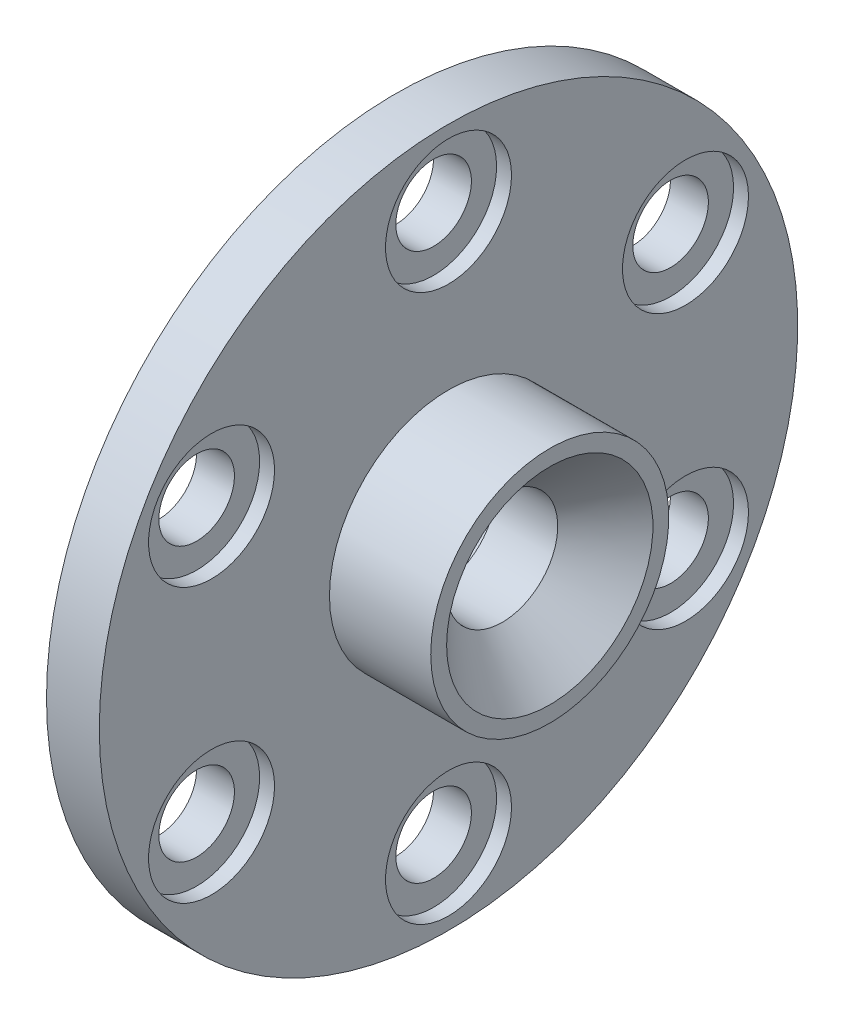
SolidWorks part; units mm, degrees
ref_plane "Front Plane" through (0, 0, 0) normal (0, 0, 1) x (1, 0, 0)
ref_plane "Top Plane" through (0, 0, 0) normal (0, 1, 0) x (1, 0, 0)
ref_plane "Right Plane" through (0, 0, 0) normal (1, 0, 0) x (0, 0, -1)
sketch "Sketch2" plane through (0, 0, 0) normal (0, 0, 1) x (1, 0, 0)
  line L0 (0, 0) -> (58.591, 0) construction
  line L2 (0, 0) -> (18.4, 0)
  line L3 (0, 0) -> (0, 2.5)
  line L4 (0, 2.5) -> (18.4, 2.5)
  line L5 (18.4, 0) -> (18.4, 2.5)
  line L6 (6.0094, 2.5) -> (6.0094, 6)
  line L11 (6.0094, 6) -> (9.9794, 6)
  line L16 (12.9794, 6) -> (12.9794, 3)
  line L17 (12.9794, 3) -> (13.6398, 3)
  line L18 (13.6398, 3) -> (13.6398, 2.5)
  line L19 (13.6398, 2.5) -> (6.0094, 2.5)
  line L22 (13.6398, 2.5) -> (16.1198, 2.5)
  line L23 (13.6398, 2.5) -> (13.6398, 4)
  line L24 (13.6398, 4) -> (16.1198, 4)
  line L25 (16.1198, 2.5) -> (16.1198, 4)
  line L27 (6.0094, 6) -> (9.9794, 6)
  line L28 (6.0094, 6) -> (6.0094, 9)
  line L29 (6.0094, 9) -> (9.9794, 9)
  line L30 (9.9794, 6) -> (9.9794, 9)
  line L31 (6.0094, 9) -> (6.0094, 8.25)
  line L32 (6.0094, 8.25) -> (5.0094, 8.25)
  line L33 (8.6609, 22.001) -> (8.6609, 12.476) construction
  line L34 (5.0094, 12.476) -> (12.3124, 12.476)
  line L35 (9.9794, 9) -> (12.3124, 9)
  line L36 (5.0094, 7.9375) -> (1.8344, 7.9375)
  line L37 (5.0094, 8.25) -> (5.0094, 12.476)
  line L38 (5.0094, 7.9375) -> (5.0094, 13.9365)
  line L39 (5.0094, 13.9365) -> (1.8344, 13.9365)
  line L40 (1.8344, 7.9375) -> (1.8344, 13.9365)
  line L41 (5.0094, 22.001) -> (12.3124, 22.001)
  line L42 (5.0094, 22.001) -> (5.0094, 30.1625)
  line L43 (5.0094, 30.1625) -> (12.3124, 30.1625)
  line L44 (12.3124, 22.001) -> (12.3124, 30.1625)
  line L49 (16.6398, 22.001) -> (16.6398, 7.5)
  line L51 (23.0198, 7.5) -> (23.0198, 6.5)
  line L54 (16.1198, 4) -> (13.6398, 4)
  line L56 (18.0398, 7.5) -> (23.0198, 7.5)
  line L57 (13.3124, 22.001) -> (16.6398, 22.001)
  line L58 (16.1198, 3.5) -> (20.0198, 3.5)
  line L59 (29.9098, 14) -> (26.9098, 11)
  line L60 (4.0094, 31.75) -> (18.0398, 31.75)
  line L61 (18.0398, 7.5) -> (23.0198, 7.5)
  line L62 (18.0398, 7.5) -> (18.0398, 12)
  line L63 (18.0398, 12) -> (23.0198, 12)
  line L64 (23.0198, 7.5) -> (23.0198, 12)
  line L65 (18.0398, 31.75) -> (18.0398, 12)
  line L66 (23.0198, 11) -> (26.9098, 11)
  line L67 (34.8098, 23) -> (31.3098, 19.5)
  line L68 (35.8098, 31) -> (38.7998, 33.99)
  line L69 (29.9098, 14) -> (29.9098, 15)
  line L70 (29.9098, 15) -> (22.9398, 15)
  line L71 (22.9398, 15) -> (21.0398, 15)
  line L72 (18.0398, 7.5) -> (16.6398, 7.5)
  line L73 (21.0398, 15) -> (21.0398, 43)
  line L74 (19.5798, 40) -> (9.6198, 40)
  line L75 (9.6198, 40) -> (4.0094, 40)
  line L76 (21.0398, 43) -> (19.5798, 43)
  line L77 (22.9398, 15) -> (29.9098, 15)
  line L78 (22.9398, 15) -> (22.9398, 21)
  line L79 (22.9398, 21) -> (29.9098, 21)
  line L80 (29.9098, 15) -> (29.9098, 21)
  line L81 (9.6198, 40) -> (19.5798, 40)
  line L82 (9.6198, 40) -> (9.6198, 50)
  line L83 (9.6198, 50) -> (19.5798, 50)
  line L84 (19.5798, 40) -> (19.5798, 50)
  line L85 (4.0094, 40) -> (4.0094, 31.75)
  line L86 (12.9794, 3) -> (12.9794, 2.5)
  line L87 (31.3098, 19.5) -> (29.9098, 19.5)
  line L88 (21.4694, 63.5) -> (21.4694, 51.308)
  line L89 (21.4694, 63.5) -> (25.9398, 63.5)
  line L90 (25.9398, 63.5) -> (25.9398, 25)
  line L91 (27.8398, 25) -> (25.9398, 25)
  line L92 (9.6198, 48) -> (8.1598, 48)
  line L93 (8.1598, 48) -> (8.1598, 53.476)
  line L94 (8.1598, 53.476) -> (19.5798, 53.476)
  line L95 (19.5798, 53.476) -> (19.5798, 50)
  line L96 (13.8698, 63.001) -> (13.8698, 53.476) construction
  line L97 (8.1598, 63.001) -> (19.5798, 63.001)
  line L98 (8.1598, 63.001) -> (8.1598, 68.2625)
  line L99 (8.1598, 68.2625) -> (19.5798, 68.2625)
  line L100 (19.5798, 63.001) -> (19.5798, 68.2625)
  line L101 (12.9794, 6) -> (11.9794, 6)
  line L102 (8.1598, 44.825) -> (4.9848, 44.825)
  line L103 (8.1598, 44.825) -> (8.1598, 54.9365)
  line L104 (8.1598, 54.9365) -> (4.9848, 54.9365)
  line L106 (9.9794, 6) -> (10.8794, 6)
  line L107 (27.8398, 25) -> (34.8098, 25)
  line L108 (34.8098, 25) -> (34.8098, 23)
  line L109 (0, 0) -> (-2, 0)
  line L110 (0, 0) -> (0, 11)
  line L111 (27.8398, 25) -> (34.8098, 25)
  line L112 (27.8398, 25) -> (27.8398, 32.5)
  line L113 (27.8398, 32.5) -> (34.8098, 32.5)
  line L114 (34.8098, 25) -> (34.8098, 32.5)
  line L115 (35.8098, 31) -> (34.8098, 31)
  line L116 (27.8398, 32.5) -> (27.8398, 64.5)
  line L117 (20.5373, 74.025) -> (6.2023, 74.025)
  line L118 (6.2023, 74.025) -> (6.2023, 76.2)
  line L119 (38.7998, 47.29) -> (30.8398, 55.25)
  line L120 (0, 11) -> (-2, 11)
  line L121 (38.7998, 43.815) -> (30.8623, 43.815)
  line L123 (-4.8152, 69.85) -> (1.5348, 76.2)
  line L124 (38.7998, 47.29) -> (38.7998, 33.99)
  line L125 (-2, 0) -> (-2, 11)
  line L126 (38.7998, 37.465) -> (30.8623, 37.465)
  line L127 (30.8623, 43.815) -> (30.8623, 37.465)
  line L128 (6.0094, 2.5) -> (6.0094, 0)
  line L129 (-0.0152, 63.5) -> (-0.0152, 30)
  line L132 (4.9848, 63.5) -> (-0.0152, 63.5)
  line L136 (-1.8152, 30) -> (-11.7752, 30)
  line L138 (-13.7752, 25.4) -> (-2, 25.4)
  line L139 (-2, 25.4) -> (-2, 11.5)
  line L140 (27.8398, 64.5) -> (20.5373, 64.5)
  line L141 (-1.8152, 30) -> (-11.7752, 30)
  line L142 (-1.8152, 30) -> (-1.8152, 39)
  line L143 (-1.8152, 39) -> (-11.7752, 39)
  line L144 (-11.7752, 30) -> (-11.7752, 39)
  line L145 (20.5373, 64.5) -> (20.5373, 74.025)
  line L146 (-12.7752, 37) -> (-12.7752, 47.29)
  line L147 (-12.7752, 37) -> (-11.7752, 37)
  line L148 (30.8398, 55.25) -> (30.8398, 76.2)
  line L149 (11.9794, 6) -> (11.9794, 5.45)
  line L154 (-2, 11.5) -> (0.5, 11.5)
  line L155 (4.9848, 60.6197) -> (24.0348, 60.6197)
  line L160 (4.9848, 60.6197) -> (4.9848, 55.8572)
  line L161 (4.9848, 55.8572) -> (24.0348, 55.8572)
  line L166 (24.0348, 60.6197) -> (24.0348, 55.8572)
  line L167 (4.9848, 60.6197) -> (24.0348, 55.8572) construction
  line L172 (4.9848, 55.8572) -> (24.0348, 60.6197) construction
  line L173 (24.0348, 62.2072) -> (25.9398, 62.2072)
  line L174 (11.9794, 5.45) -> (10.8794, 5.45)
  line L175 (10.8794, 6) -> (10.8794, 5.45)
  line L176 (24.0348, 62.2072) -> (24.0348, 54.2697)
  line L177 (24.0348, 54.2697) -> (25.9398, 54.2697)
  line L178 (25.9398, 62.2072) -> (25.9398, 54.2697)
  line L179 (24.0348, 62.2072) -> (25.9398, 54.2697) construction
  line L180 (24.0348, 54.2697) -> (25.9398, 62.2072) construction
  line L181 (3, 19.6197) -> (15.7, 19.6197)
  line L182 (3, 19.6197) -> (3, 14.8572)
  line L183 (3, 14.8572) -> (15.7, 14.8572)
  line L184 (15.7, 19.6197) -> (15.7, 14.8572)
  line L185 (3, 19.6197) -> (15.7, 14.8572) construction
  line L186 (3, 14.8572) -> (15.7, 19.6197) construction
  line L187 (15.7, 21.2072) -> (16.6398, 21.2072)
  line L188 (15.7, 21.2072) -> (15.7, 13.2697)
  line L189 (15.7, 13.2697) -> (16.6398, 13.2697)
  line L190 (16.6398, 21.2072) -> (16.6398, 13.2697)
  line L191 (15.7, 21.2072) -> (16.6398, 13.2697) construction
  line L192 (15.7, 13.2697) -> (16.6398, 21.2072) construction
  line L193 (0.5, 11.5) -> (0.5, 6.9375)
  line L194 (0.5, 6.9375) -> (1.8344, 6.9375)
  line L195 (23.0198, 6.5) -> (20.0198, 3.5)
  line L196 (4.9848, 63.5) -> (4.9848, 54.9365)
  line L197 (3, 43.825) -> (4.9848, 43.825)
  line L198 (1.8344, 6.9375) -> (1.8344, 7.9375)
  line L199 (6.0094, 0) -> (12.9794, 0)
  line L200 (12.9794, 0) -> (12.9794, 2.5)
  line L201 (18.0398, 31.75) -> (18.0398, 35.875)
  line L202 (18.0398, 35.875) -> (21.0398, 35.875)
  line L203 (30.8398, 76.2) -> (6.2023, 76.2)
  line L204 (2.7573, 69.85) -> (7.2023, 69.85) construction
  line L205 (7.2023, 67.4688) -> (26.2523, 67.4688)
  line L206 (7.2023, 74.025) -> (7.2023, 64.5)
  line L207 (7.2023, 64.5) -> (-1.8152, 64.5)
  line L208 (-1.8152, 64.5) -> (-1.8152, 39)
  line L209 (-12.7752, 47.29) -> (-4.8152, 55.25)
  line L210 (-4.8152, 55.25) -> (-4.8152, 69.85)
  line L211 (7.2023, 67.4688) -> (7.2023, 72.2312)
  line L212 (7.2023, 72.2312) -> (26.2523, 72.2313)
  line L213 (26.2523, 67.4688) -> (26.2523, 72.2313)
  line L214 (26.2523, 73.8187) -> (30.8398, 73.8187)
  line L215 (26.2523, 73.8187) -> (26.2523, 65.8813)
  line L216 (26.2523, 65.8813) -> (30.8398, 65.8813)
  line L217 (30.8398, 73.8187) -> (30.8398, 65.8813)
  line L218 (2.7573, 72.2313) -> (24.9823, 72.2313)
  line L219 (2.7573, 72.2313) -> (2.7573, 67.4687)
  line L220 (2.7573, 67.4687) -> (24.9823, 67.4687)
  line L221 (24.9823, 72.2313) -> (24.9823, 67.4687)
  line L222 (24.9823, 69.85) -> (20.5373, 69.85) construction
  line L223 (21.4694, 51.308) -> (22.9398, 51.308)
  line L224 (22.9398, 51.308) -> (22.9398, 21)
  line L225 (13.6398, 4) -> (13.6398, 12.2697)
  line L226 (13.6398, 12.2697) -> (13.3124, 12.2697)
  line L227 (13.3124, 12.2697) -> (13.3124, 22.001)
  line L228 (12.3124, 9) -> (12.3124, 12.476)
  line L229 (-1.8152, 30) -> (-0.0152, 30)
  line L230 (8.1598, 65.6317) -> (2.7573, 65.6317) construction
  line L231 (19.5798, 65.6317) -> (24.9823, 65.6317) construction
  line L232 (1.5348, 76.2) -> (6.2023, 76.2)
  line L233 (-11.7752, 30) -> (-13.7752, 30)
  line L234 (-13.7752, 30) -> (-13.7752, 25.4)
  line L235 (3, 13.9365) -> (3, 43.825)
  line L236 (4.9848, 54.9365) -> (4.9848, 44.825)
  line L237 (4.9848, 43.825) -> (4.9848, 44.825)
  circle A0 centre (26.8898, 25.95) radius 0.95
  circle A1 centre (21.9898, 15.95) radius 0.95
  circle A2 centre (17.3398, 8.2) radius 0.7
  circle A3 centre (10.4294, 6.45) radius 0.45
  circle A4 centre (-0.9152, 30.9) radius 0.9
  point P7 (24.9873, 58.2385)
  point P131 (16.1699, 17.2385)
  point P135 (14.5098, 58.2385)
  point P146 (9.35, 17.2385)
sketch "Sketch3" plane through (0, 0, 0) normal (0, 0, 1) x (1, 0, 0)
  line L0 (13.3124, 22.001) -> (16.6398, 22.001) construction
  line L1 (16.6398, 22.001) -> (16.6398, 7.5) construction
  line L4 (23.0198, 7.5) -> (23.0198, 6.5) construction
  line L5 (18.0398, 7.5) -> (23.0198, 7.5) construction
  line L7 (13.6398, 4) -> (16.1198, 4) construction
  line L8 (16.1198, 2.5) -> (16.1198, 4) construction
  line L9 (16.1198, 3.5) -> (20.0198, 3.5) construction
  line L10 (23.0198, 6.5) -> (20.0198, 3.5) construction
  line L11 (13.3124, 22.001) -> (16.6398, 22.001)
  line L12 (16.6398, 22.001) -> (16.6398, 7.5)
  line L15 (23.0198, 7.5) -> (23.0198, 6.5)
  line L16 (18.0398, 7.5) -> (23.0198, 7.5)
  line L18 (13.6398, 4) -> (16.1198, 4)
  line L19 (16.1198, 3.5) -> (16.1198, 4)
  line L20 (16.1198, 3.5) -> (20.0198, 3.5)
  line L21 (23.0198, 6.5) -> (20.0198, 3.5)
  line L22 (18.0398, 7.5) -> (16.6398, 7.5) construction
  line L23 (13.6398, 4) -> (13.6398, 12.2697) construction
  line L24 (13.6398, 12.2697) -> (13.3124, 12.2697) construction
  line L25 (13.3124, 12.2697) -> (13.3124, 22.001) construction
  line L26 (18.0398, 7.5) -> (16.6398, 7.5)
  line L27 (13.6398, 4) -> (13.6398, 12.2697)
  line L28 (13.6398, 12.2697) -> (13.3124, 12.2697)
  line L29 (13.3124, 12.2697) -> (13.3124, 22.001)
revolve "Revolve1" add sketch "Sketch3" angle 360 about L0
sketch "Sketch4" plane through (0, 0, 0) normal (1, 0, 0) x (0, 0, -1)
  line L0 (0, 0) -> (0, 69.85) construction
  line L1 (0, 0) -> (13.6271, 68.5079) construction
  line L2 (0, 0) -> (0, 58.2385) construction
  line L3 (0, 0) -> (50.436, 29.1192) construction
  line L4 (0, 0) -> (0, 31.75) construction
  line L5 (0, 0) -> (12.1502, 29.3332) construction
  line L6 (0, 0) -> (0, 17.2385) construction
  line L7 (0, 0) -> (14.929, 8.6192) construction
  line L8 (0, 0) -> (0, 58.2385) construction
  line L9 (0, 0) -> (50.436, 29.1192) construction
  line L10 (0, 0) -> (5.9583, 29.9542) construction
  line L11 (0, 0) -> (16.9677, 25.394) construction
  circle A0 centre (0, 0) radius 69.85 construction
  circle A1 centre (0, 0) radius 58.2385 construction
  circle A2 centre (0, 0) radius 31.75 construction
  circle A3 centre (0, 0) radius 17.2385 construction
  circle A4 centre (0, 69.85) radius 3.175
  circle A5 centre (0, 58.2385) radius 4.7625
  circle A6 centre (0, 31.75) radius 3.175
  circle A7 centre (0, 17.2385) radius 4.7625
  circle A8 centre (13.6271, 68.5079) radius 3.175
  circle A9 centre (26.7304, 64.533) radius 3.175
  circle A10 centre (38.8066, 58.0782) radius 3.175
  circle A11 centre (49.3914, 49.3914) radius 3.175
  circle A12 centre (58.0782, 38.8066) radius 3.175
  circle A13 centre (64.533, 26.7304) radius 3.175
  circle A14 centre (68.5079, 13.6271) radius 3.175
  circle A15 centre (69.85, 0) radius 3.175
  circle A16 centre (68.5079, -13.6271) radius 3.175
  circle A17 centre (64.533, -26.7304) radius 3.175
  circle A18 centre (58.0782, -38.8066) radius 3.175
  circle A19 centre (49.3914, -49.3914) radius 3.175
  circle A20 centre (38.8066, -58.0782) radius 3.175
  circle A21 centre (26.7304, -64.533) radius 3.175
  circle A22 centre (13.6271, -68.5079) radius 3.175
  circle A23 centre (0, -69.85) radius 3.175
  circle A24 centre (-13.6271, -68.5079) radius 3.175
  circle A25 centre (-26.7304, -64.533) radius 3.175
  circle A26 centre (-38.8066, -58.0782) radius 3.175
  circle A27 centre (-49.3914, -49.3914) radius 3.175
  circle A28 centre (-58.0782, -38.8066) radius 3.175
  circle A29 centre (-64.533, -26.7304) radius 3.175
  circle A30 centre (-68.5079, -13.6271) radius 3.175
  circle A31 centre (-69.85, 0) radius 3.175
  circle A32 centre (-68.5079, 13.6271) radius 3.175
  circle A33 centre (-64.533, 26.7304) radius 3.175
  circle A34 centre (-58.0782, 38.8066) radius 3.175
  circle A35 centre (-49.3914, 49.3914) radius 3.175
  circle A36 centre (-38.8066, 58.0782) radius 3.175
  circle A37 centre (-26.7304, 64.533) radius 3.175
  circle A38 centre (-13.6271, 68.5079) radius 3.175
  circle A47 centre (50.436, 29.1192) radius 4.7625
  circle A48 centre (50.436, -29.1192) radius 4.7625
  circle A49 centre (0, -58.2385) radius 4.7625
  circle A50 centre (-50.436, -29.1192) radius 4.7625
  circle A51 centre (-50.436, 29.1192) radius 4.7625
  circle A58 centre (12.1502, 29.3332) radius 3.175
  circle A59 centre (22.4506, 22.4506) radius 3.175
  circle A60 centre (29.3332, 12.1502) radius 3.175
  circle A61 centre (31.75, 0) radius 3.175
  circle A62 centre (29.3332, -12.1502) radius 3.175
  circle A63 centre (22.4506, -22.4506) radius 3.175
  circle A64 centre (12.1502, -29.3332) radius 3.175
  circle A65 centre (0, -31.75) radius 3.175
  circle A66 centre (-12.1502, -29.3332) radius 3.175
  circle A67 centre (-22.4506, -22.4506) radius 3.175
  circle A68 centre (-29.3332, -12.1502) radius 3.175
  circle A69 centre (-31.75, 0) radius 3.175
  circle A70 centre (-29.3332, 12.1502) radius 3.175
  circle A71 centre (-22.4506, 22.4506) radius 3.175
  circle A72 centre (14.929, 8.6192) radius 4.7625
  circle A73 centre (14.929, -8.6192) radius 4.7625
  circle A74 centre (0, -17.2385) radius 4.7625
  circle A75 centre (-14.929, -8.6192) radius 4.7625
  circle A76 centre (-14.929, 8.6192) radius 4.7625
  circle A77 centre (0, 0) radius 50
  circle A78 centre (0, 0) radius 9
  circle A79 centre (-12.1502, 29.3332) radius 3.175
  circle A80 centre (0, 0) radius 76.2
  circle A81 centre (0, 0) radius 74.025
  circle A82 centre (0, 69.85) radius 3.9687
  circle A83 centre (49.3914, 49.3914) radius 3.9687
  circle A84 centre (69.85, 0) radius 3.9688
  circle A85 centre (49.3914, -49.3914) radius 3.9687
  circle A86 centre (0, -69.85) radius 3.9687
  circle A87 centre (-49.3914, -49.3914) radius 3.9687
  circle A88 centre (-69.85, 0) radius 3.9688
  circle A89 centre (-49.3914, 49.3914) radius 3.9687
  circle A90 centre (0, 69.85) radius 2.3812
  circle A91 centre (13.6271, 68.5079) radius 2.3812
  circle A92 centre (26.7304, 64.533) radius 2.3813
  circle A93 centre (38.8066, 58.0782) radius 2.3812
  circle A94 centre (49.3914, 49.3914) radius 2.3812
  circle A95 centre (58.0782, 38.8066) radius 2.3812
  circle A96 centre (64.533, 26.7304) radius 2.3813
  circle A97 centre (68.5079, 13.6271) radius 2.3813
  circle A98 centre (69.85, 0) radius 2.3813
  circle A99 centre (68.5079, -13.6271) radius 2.3813
  circle A100 centre (64.533, -26.7304) radius 2.3813
  circle A101 centre (58.0782, -38.8066) radius 2.3812
  circle A102 centre (49.3914, -49.3914) radius 2.3812
  circle A103 centre (38.8066, -58.0782) radius 2.3812
  circle A104 centre (26.7304, -64.533) radius 2.3813
  circle A105 centre (13.6271, -68.5079) radius 2.3812
  circle A106 centre (0, -69.85) radius 2.3812
  circle A107 centre (-13.6271, -68.5079) radius 2.3812
  circle A108 centre (-26.7304, -64.533) radius 2.3813
  circle A109 centre (-38.8066, -58.0782) radius 2.3812
  circle A110 centre (-49.3914, -49.3914) radius 2.3812
  circle A111 centre (-58.0782, -38.8066) radius 2.3812
  circle A112 centre (-64.533, -26.7304) radius 2.3812
  arc A113 (3.0399, 30.8338) -> (8.9911, 29.65) centre (5.9583, 29.9542) cw
  arc A114 (14.6081, 27.3234) -> (19.6532, 23.9523) centre (16.9677, 25.394) cw
  arc A115 (23.9523, 19.6532) -> (27.3234, 14.6081) centre (25.394, 16.9677) cw
  arc A116 (29.65, 8.9911) -> (30.8338, 3.0399) centre (29.9542, 5.9583) cw
  arc A117 (30.8338, -3.0399) -> (29.65, -8.9911) centre (29.9542, -5.9583) cw
  arc A118 (27.3234, -14.6081) -> (23.9523, -19.6532) centre (25.394, -16.9677) cw
  arc A119 (19.6532, -23.9523) -> (14.6081, -27.3234) centre (16.9677, -25.394) cw
  arc A120 (8.9911, -29.65) -> (3.0399, -30.8338) centre (5.9583, -29.9542) cw
  arc A121 (-3.0399, -30.8338) -> (-8.9911, -29.65) centre (-5.9583, -29.9542) cw
  arc A122 (-14.6081, -27.3234) -> (-19.6532, -23.9523) centre (-16.9677, -25.394) cw
  arc A123 (-23.9523, -19.6532) -> (-27.3234, -14.6081) centre (-25.394, -16.9677) cw
  arc A124 (-29.65, -8.9911) -> (-30.8338, -3.0399) centre (-29.9542, -5.9583) cw
  arc A125 (-30.8338, 3.0399) -> (-29.65, 8.9911) centre (-29.9542, 5.9583) cw
  arc A126 (-27.3234, 14.6081) -> (-23.9523, 19.6532) centre (-25.394, 16.9677) cw
  arc A127 (-19.6532, 23.9523) -> (-14.6081, 27.3234) centre (-16.9677, 25.394) cw
  arc A128 (-8.9911, 29.65) -> (-3.0399, 30.8338) centre (-5.9583, 29.9542) cw
  arc A129 (26.9875, 0) -> (26.9932, 0.1932) centre (30.2705, 0) cw
  arc A130 (65.0988, 0.2771) -> (65.0875, 0) centre (68.4964, 0) ccw
  circle A131 centre (1.5875, 0) radius 40
  circle A132 centre (1.5875, 0) radius 2.5
  circle A133 centre (1.5875, 0) radius 3
  circle A134 centre (1.5875, 0) radius 43
  circle A135 centre (-68.5079, -13.6271) radius 2.3813
  circle A136 centre (-69.85, 0) radius 2.3813
  circle A137 centre (-68.5079, 13.6271) radius 2.3813
  circle A138 centre (-64.533, 26.7304) radius 2.3812
  circle A139 centre (-58.0782, 38.8066) radius 2.3812
  circle A140 centre (-49.3914, 49.3914) radius 2.3812
  circle A141 centre (-38.8066, 58.0782) radius 2.3812
  circle A142 centre (-26.7304, 64.533) radius 2.3813
  circle A143 centre (-13.6271, 68.5079) radius 2.3812
  circle A144 centre (0, 58.2385) radius 2.3812
  circle A145 centre (0, 58.2385) radius 3.9688
  circle A146 centre (50.436, 29.1192) radius 3.9688
  circle A147 centre (50.436, 29.1192) radius 2.3813
  circle A148 centre (50.436, -29.1192) radius 3.9687
  circle A149 centre (50.436, -29.1192) radius 2.3812
  circle A150 centre (0, -58.2385) radius 3.9687
  circle A151 centre (0, -58.2385) radius 2.3812
  circle A152 centre (-50.436, -29.1192) radius 3.9687
  circle A153 centre (-50.436, -29.1192) radius 2.3812
  circle A154 centre (-50.436, 29.1192) radius 3.9687
  circle A155 centre (-50.436, 29.1192) radius 2.3812
  spline S1 degree 4 number of poles 499 (26.9875, 0) -> (26.9932, 0.1932)
  spline S3 degree 4 number of poles 617 (65.0875, 0) -> (65.0988, 0.2771)
  point P116 (0, 0)
  point P225 (0, 0)
sketch "Sketch5" plane through (0, 0, 0) normal (1, 0, 0) x (0, 0, -1)
  circle A0 centre (-14.929, 8.6192) radius 4.7625 construction
  circle A1 centre (-14.929, -8.6192) radius 4.7625 construction
  circle A2 centre (0, -17.2385) radius 4.7625 construction
  circle A3 centre (14.929, -8.6192) radius 4.7625 construction
  circle A4 centre (14.929, 8.6192) radius 4.7625 construction
  circle A5 centre (0, 17.2385) radius 4.7625 construction
  circle A6 centre (-14.929, 8.6192) radius 4.7625
  circle A7 centre (-14.929, -8.6192) radius 4.7625
  circle A8 centre (0, -17.2385) radius 4.7625
  circle A9 centre (14.929, -8.6192) radius 4.7625
  circle A10 centre (14.929, 8.6192) radius 4.7625
  circle A11 centre (0, 17.2385) radius 4.7625
  circle A12 centre (0, 17.2385) radius 2.3813
  circle A13 centre (14.929, 8.6192) radius 2.3813
  circle A14 centre (14.929, -8.6192) radius 2.3813
  circle A15 centre (0, -17.2385) radius 2.3813
  circle A16 centre (-14.929, -8.6192) radius 2.3813
  circle A17 centre (-14.929, 8.6192) radius 2.3813
  dimension "D1" = 4.7625
extrude "Cut-Extrude1" cut sketch "Sketch5" along normal through all contours A17 | A12 | A13 | A14 | A15 | A16 region at (0, 17.2385, 0) region at (0, 8.6192, -14.929) region at (0, -8.6192, -14.929) region at (0, -17.2385, 0) region at (0, -8.6192, 14.929) region at (0, 8.6192, 14.929)
sketch "Sketch6" plane through (16.6398, 0, 0) normal (1, 0, 0) x (0, 0, -1)
  circle A0 centre (0, 17.2385) radius 3.9688
  circle A1 centre (14.929, 8.6192) radius 3.9688
  circle A2 centre (14.929, -8.6192) radius 3.9687
  circle A3 centre (0, -17.2385) radius 3.9688
  circle A4 centre (-14.929, -8.6192) radius 3.9687
  circle A5 centre (-14.929, 8.6192) radius 3.9687
  dimension "D1" = 7.9375
extrude "Cut-Extrude2" cut sketch "Sketch6" against normal up to vertex (0.9398 mm away) up to point (15.7, 21.2072, 0)
